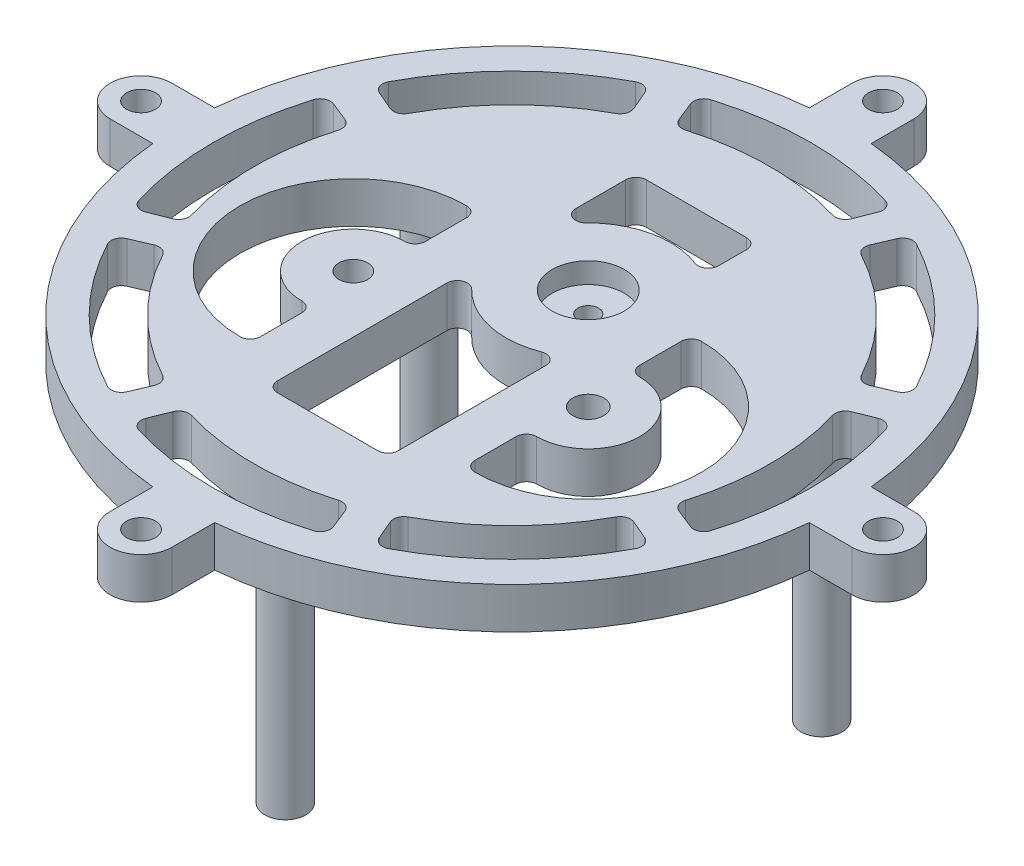
SolidWorks part; units mm, degrees
ref_plane "Front Plane" through (0, 0, 0) normal (0, 0, 1) x (1, 0, 0)
ref_plane "Top Plane" through (0, 0, 0) normal (0, 1, 0) x (1, 0, 0)
ref_plane "Right Plane" through (0, 0, 0) normal (1, 0, 0) x (0, 0, -1)
ref_axis "Center Axis" through (0, 0.65, 0) along (0, -1, 0)
sketch "STR Point" plane through (0, 0, 0) normal (0, 1, 0) x (1, 0, 0)
  point P0 (0.8, 2.9)
  dimension "D1" = 0.8
  dimension "D2" = 2.9
ref_axis "STR Axis" through (0.8, 0, -2.9) along (0, 1, 0)
sketch "Sketch1" plane through (0, 0, 0) normal (0, 1, 0) x (1, 0, 0)
  circle A0 centre (0, -11) radius 1
  dimension "D1" = 11
extrude "Boss-Extrude1" add sketch "Sketch1" against normal blind 13
sketch "Sketch2" plane through (0, 0, 0) normal (0, 1, 0) x (1, 0, 0)
  line L0 (-5.2, 3) -> (-5.2, 1)
  line L1 (-5.2, -5) -> (-5.2, -7)
  line L2 (2.9345, -1.2927) -> (2.9345, -8.4498)
  line L3 (-18, 1.5) -> (-15.9295, 1.5)
  line L4 (-18, -1.5) -> (-15.9295, -1.5)
  line L5 (0, 16.5) -> (0, -18) construction
  line L6 (-18, 0) -> (16.5, 0) construction
  line L7 (1.5, 18) -> (1.5, 15.9295)
  line L8 (-1.5, 18) -> (-1.5, 15.9295)
  line L9 (18, 1.5) -> (15.9295, 1.5)
  line L10 (18, -1.5) -> (15.9295, -1.5)
  line L11 (1.5, -18) -> (1.5, -15.9295)
  line L12 (-1.5, -18) -> (-1.5, -15.9295)
  line L13 (-2.4345, 8.9498) -> (2.4345, 8.9498)
  line L14 (-2.9345, 8.4498) -> (-2.9345, 6.0286)
  line L15 (-2.4345, -8.9498) -> (2.4345, -8.9498)
  line L16 (2.9345, 8.4498) -> (2.9345, 7.0927)
  line L17 (-2.9345, 8.9498) -> (2.9345, -8.9498) construction
  line L18 (-2.9345, -8.9498) -> (2.9345, 8.9498) construction
  line L19 (-2.9345, -0.2286) -> (-2.9345, -8.4498)
  line L20 (5.2, -5) -> (5.2, -7)
  line L21 (5.2, 3) -> (5.2, 1)
  arc A0 (-15.9295, -1.5) -> (-1.5, -15.9295) centre (0, 0) ccw
  circle A1 centre (0.8, 2.9) radius 1.75
  arc A2 (-5.7, 0.5) -> (-5.2, 1) centre (-5.7, 1) ccw
  arc A3 (-18, 1.5) -> (-18, -1.5) centre (-18, 0) ccw
  arc A4 (1.5, 18) -> (-1.5, 18) centre (0, 18) ccw
  arc A5 (18, -1.5) -> (18, 1.5) centre (18, 0) ccw
  arc A6 (-1.5, -18) -> (1.5, -18) centre (0, -18) ccw
  arc A7 (1.5, -15.9295) -> (15.9295, -1.5) centre (0, 0) ccw
  arc A8 (15.9295, 1.5) -> (1.5, 15.9295) centre (0, 0) ccw
  arc A9 (-1.5, 15.9295) -> (-15.9295, 1.5) centre (0, 0) ccw
  circle A10 centre (0, 18) radius 0.7
  circle A11 centre (18, 0) radius 0.7
  circle A12 centre (-18, 0) radius 0.7
  circle A13 centre (0, -18) radius 0.7
  circle A14 centre (-5.7, -2) radius 0.7
  circle A15 centre (5.7, -2) radius 0.75
  arc A16 (-5.2, 3) -> (-5.7, 3.5) centre (-5.7, 3) ccw
  arc A17 (-5.2, -5) -> (-5.7, -4.5) centre (-5.7, -5) ccw
  arc A18 (-5.7, -7.5) -> (-5.2, -7) centre (-5.7, -7) ccw
  arc A19 (-5.7, 3.5) -> (-5.7, -7.5) centre (-5.7, -2) ccw
  arc A20 (-5.7, 0.5) -> (-5.7, -4.5) centre (-5.7, -2) ccw
  arc A21 (2.2529, 6.6268) -> (-2.0751, 5.681) centre (0.8, 2.9) ccw
  arc A22 (-2.9345, -8.4498) -> (-2.4345, -8.9498) centre (-2.4345, -8.4498) ccw
  arc A23 (2.4345, -8.9498) -> (2.9345, -8.4498) centre (2.4345, -8.4498) ccw
  arc A24 (2.4345, 8.9498) -> (2.9345, 8.4498) centre (2.4345, 8.4498) cw
  arc A25 (-2.4345, 8.9498) -> (-2.9345, 8.4498) centre (-2.4345, 8.4498) ccw
  arc A26 (2.2529, -0.8268) -> (2.9345, -1.2927) centre (2.4345, -1.2927) cw
  arc A27 (2.2529, 6.6268) -> (2.9345, 7.0927) centre (2.4345, 7.0927) ccw
  arc A28 (-2.0751, 0.119) -> (2.2529, -0.8268) centre (0.8, 2.9) ccw
  arc A29 (-2.0751, 0.119) -> (-2.9345, -0.2286) centre (-2.4345, -0.2286) ccw
  arc A30 (-2.0751, 5.681) -> (-2.9345, 6.0286) centre (-2.4345, 6.0286) cw
  arc A31 (5.7, 0.5) -> (5.7, -4.5) centre (5.7, -2) cw
  arc A32 (5.7, 3.5) -> (5.7, -7.5) centre (5.7, -2) cw
  arc A33 (5.7, -7.5) -> (5.2, -7) centre (5.7, -7) cw
  arc A34 (5.2, -5) -> (5.7, -4.5) centre (5.7, -5) cw
  arc A35 (5.2, 3) -> (5.7, 3.5) centre (5.7, 3) cw
  arc A36 (5.7, 0.5) -> (5.2, 1) centre (5.7, 1) cw
  point P5 (-5.7, -5)
  point P6 (-5.7, -7)
  point P7 (-5.7, 1)
  point P8 (-5.7, 3)
  point P73 (2.9345, -0.4829)
  point P80 (-2.9345, 1.4669)
  dimension "D1" = 18
  dimension "D2" = 18
  dimension "D5" = 5.7
  dimension "D9" = 3
  dimension "D10" = 2
  dimension "D11" = 3
  dimension "D13" = 0.5
  dimension "D14" = 0.5
  dimension "D15" = 0.5
  dimension "D3" = 18
  dimension "D4" = 18
  dimension "D6" = 5.7
  dimension "D7" = 2
  dimension "D8" = 2
  dimension "D12" = 2
extrude "Boss-Extrude2" add sketch "Sketch2" along normal blind 2
pattern_circular "CirPattern2" count 3 over 360 about axis through (0, 0.65, 0) along (0, -1, 0) of "Boss-Extrude1" reverse direction yes
sketch "Sketch5" plane through (0, 0, 0) normal (0, -1, 0) x (1, 0, 0)
  circle A0 centre (0.8, -2.9) radius 1.75
  circle A1 centre (0.8, -2.9) radius 0.5
extrude "Boss-Extrude3" add sketch "Sketch5" against normal blind 1
sketch "Sketch8" plane through (0, 2, 0) normal (0, 1, 0) x (1, 0, 0)
  line L0 (4.1769, 12.281) -> (4.551, 13.2135)
  line L1 (-4.1769, 12.281) -> (-4.551, 13.2135)
  arc A0 (4.2328, 13.8779) -> (-4.2328, 13.8779) centre (0, 0) ccw
  arc A1 (3.5702, 11.9879) -> (-3.5702, 11.9879) centre (0, 0) ccw
  arc A2 (3.5702, 11.9879) -> (4.1769, 12.281) centre (3.7129, 12.4671) ccw
  arc A3 (4.551, 13.2135) -> (4.2328, 13.8779) centre (4.087, 13.3996) ccw
  arc A4 (-4.551, 13.2135) -> (-4.2328, 13.8779) centre (-4.087, 13.3996) cw
  arc A5 (-3.5702, 11.9879) -> (-4.1769, 12.281) centre (-3.7129, 12.4671) cw
  point P10 (4.75, 13.7095)
  point P13 (-4.75, 13.7095)
  dimension "D1" = 4.75
  dimension "D3" = 0.5
  dimension "D2" = 4.75
extrude "Cut-Extrude1" cut sketch "Sketch8" against normal up to next
pattern_circular "CirPattern3" count 8 over 360 about axis through (0, 0.65, 0) along (0, -1, 0) of "Cut-Extrude1"
